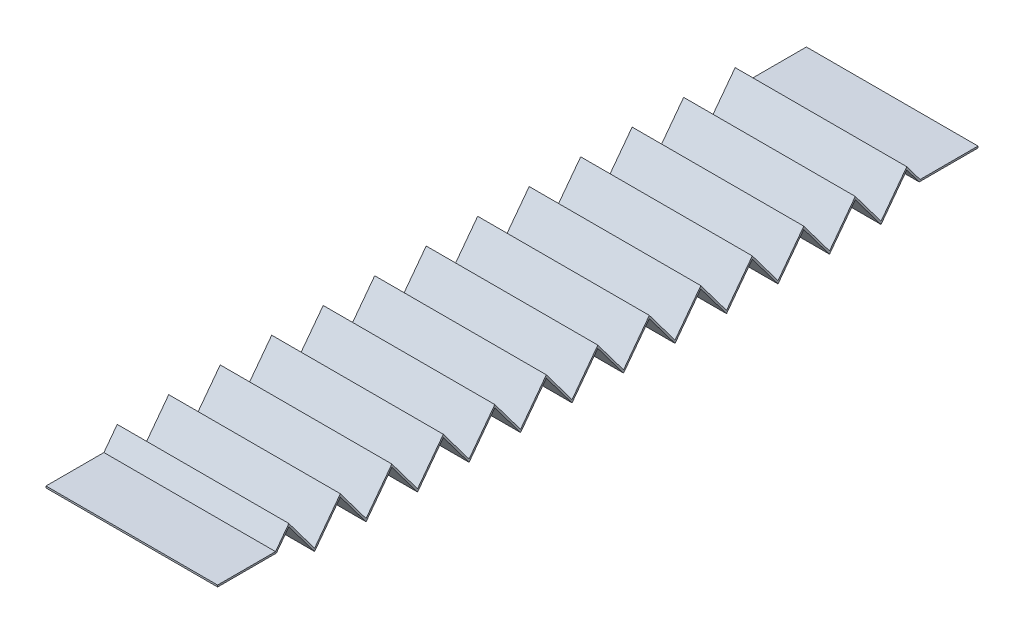
SolidWorks part; units mm, degrees
ref_plane "Front Plane" through (0, 0, 0) normal (0, 0, 1) x (1, 0, 0)
ref_plane "Top Plane" through (0, 0, 0) normal (0, 1, 0) x (1, 0, 0)
ref_plane "Right Plane" through (0, 0, 0) normal (1, 0, 0) x (0, 0, -1)
sketch "Sketch2" plane through (0, 0, 0) normal (0, 0, 1) x (1, 0, 0)
  line L1 (-27.5, 10) -> (27.5, 10)
  line L2 (-27.5, 10) -> (-27.5, 0)
  line L3 (-27.5, 0) -> (27.5, 0)
  line L4 (27.5, 10) -> (27.5, 0)
  point P4 (0, 0)
  dimension "D1" = 10
  dimension "D2" = 55
sketch "Sketch3" plane through (0, 0, 0) normal (1, 0, 0) x (0, 0, -1)
  line L0 (0, 10) -> (221.5308, 10) construction
  line L1 (0, 0) -> (221.5308, 0) construction
  line L3 (17, 5) -> (20.7506, 10)
  line L4 (20.7506, 10) -> (28.2518, 0)
  line L5 (28.2518, 0) -> (35.7531, 10)
  line L6 (35.7531, 10) -> (43.2543, 0)
  line L7 (43.2543, 0) -> (50.7555, 10)
  line L8 (50.7555, 10) -> (58.2568, 0)
  line L9 (58.2568, 0) -> (65.758, 10)
  line L10 (65.758, 10) -> (73.2592, 0)
  line L11 (73.2592, 0) -> (80.7605, 10)
  line L12 (80.7605, 10) -> (88.2617, 0)
  line L13 (88.2617, 0) -> (95.7629, 10)
  line L14 (95.7629, 10) -> (103.2642, 0)
  line L15 (103.2642, 0) -> (110.7654, 10)
  line L16 (110.7654, 10) -> (118.2666, 0)
  line L17 (118.2666, 0) -> (125.7679, 10)
  line L18 (125.7679, 10) -> (133.2691, 0)
  line L19 (0, 10) -> (0, 0) construction
  line L20 (133.2691, 0) -> (140.7703, 10)
  line L21 (140.7703, 10) -> (148.2716, 0)
  line L22 (148.2716, 0) -> (155.7728, 10)
  line L23 (155.7728, 10) -> (163.274, 0)
  line L24 (163.274, 0) -> (170.7753, 10)
  line L25 (170.7753, 10) -> (178.2765, 0)
  line L26 (178.2765, 0) -> (185.7777, 10)
  line L27 (185.7777, 10) -> (193.279, 0)
  line L28 (193.279, 0) -> (200.7802, 10)
  line L29 (200.7802, 10) -> (204.5308, 5)
  line L30 (221.5308, 10) -> (221.5308, 0) construction
  line L31 (17, 5) -> (0, 5)
  line L32 (204.5308, 5) -> (221.5308, 5)
  line L33 (221.5308, -12.75) -> (221.5308, -19.8536) construction
  dimension "D2" = 17
  dimension "D1" = 10
  dimension "D3" = 17
extrude "Extrude-Thin1" add sketch "Sketch3" against normal mid plane 50 thin thin type mid plane wall 0.5
